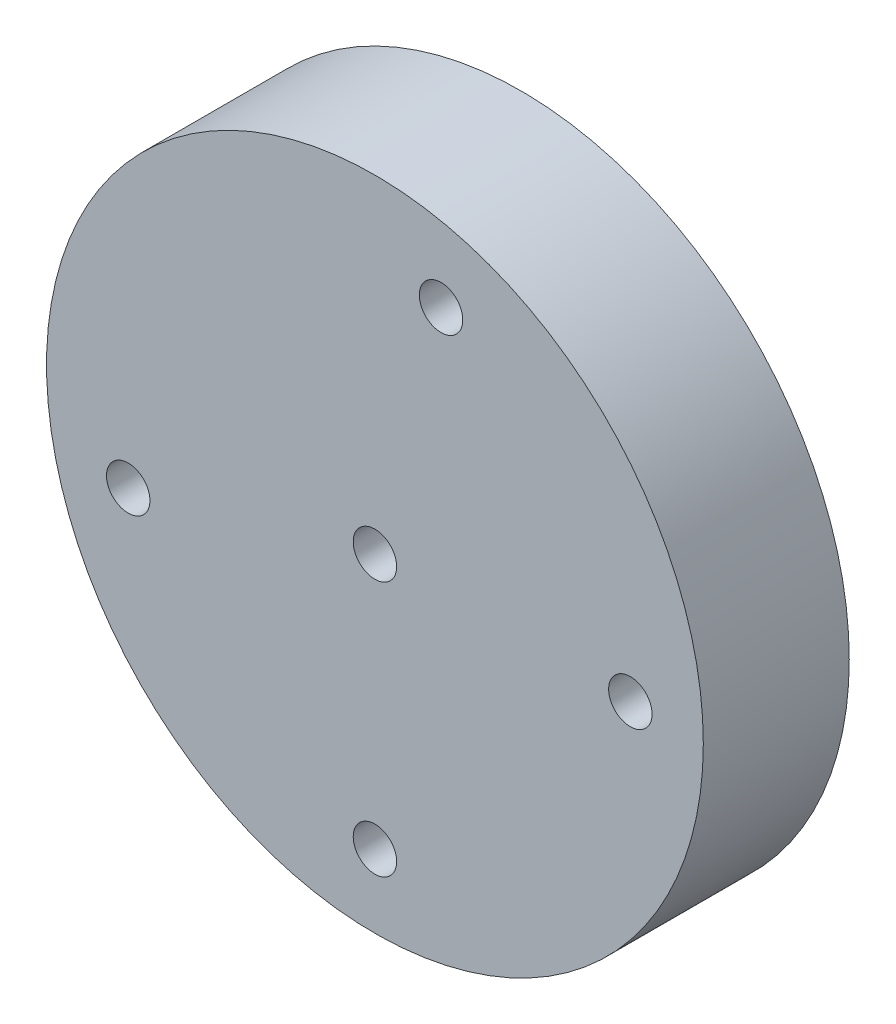
SolidWorks part; units mm, degrees
ref_plane "Front Plane" through (0, 0, 0) normal (0, 0, 1) x (1, 0, 0)
ref_plane "Top Plane" through (0, 0, 0) normal (0, 1, 0) x (1, 0, 0)
ref_plane "Right Plane" through (0, 0, 0) normal (1, 0, 0) x (0, 0, -1)
ref_axis "Z" through (0, 0, 10.5) along (0, 0, -1)
sketch "Sketch1" plane through (0, 0, 0) normal (0, 0, 1) x (1, 0, 0)
  line L0 (9.0587, 33.8074) -> (0, 0) construction
  line L1 (9.0587, 33.8074) -> (11.6469, 43.4667) construction
  line L2 (0, 0) -> (0, 45) construction
  line L3 (0, 0) -> (35, 0) construction
  line L4 (0, 0) -> (-31.8198, 31.8198) construction
  circle A1 centre (0, 0) radius 2.9766
  circle A2 centre (0, 0) radius 45
  circle A3 centre (9.0587, 33.8074) radius 2.9766
  circle A7 centre (35, 0) radius 2.9766
  circle A8 centre (0, -35) radius 2.9766
  circle A9 centre (-33.8074, -9.0587) radius 2.9766
  point P2 (-38.3948, 38.3948)
  point P7 (0, 0)
  point P11 (8.7288, 33.8941)
  point P18 (0, 0)
  point P20 (12.781, 43.1468)
  point P21 (0, 0)
  point P22 (35, 0)
  point P23 (-34.0968, -7.8999)
  point P25 (8.4059, 33.9756)
  dimension "D1" = 5.9531
  dimension "D2" = 45
  dimension "D3" = 35
  dimension "D4" = 10
  dimension "D5" = 60
extrude "Boss-Extrude1" add sketch "Sketch1" along normal blind 20
